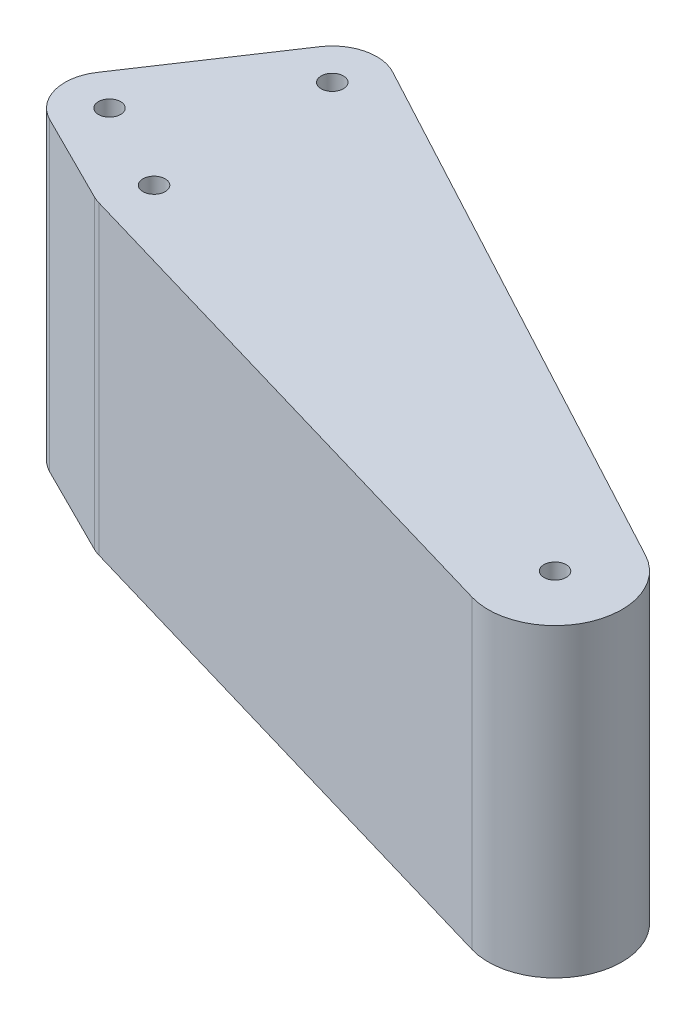
SolidWorks part; units mm, degrees
ref_plane "Front Plane" through (0, 0, 0) normal (0, 0, 1) x (1, 0, 0)
ref_plane "Top Plane" through (0, 0, 0) normal (0, 1, 0) x (1, 0, 0)
ref_plane "Right Plane" through (0, 0, 0) normal (1, 0, 0) x (0, 0, -1)
sketch "Sketch1" plane through (0, 0, 0) normal (0, 1, 0) x (1, 0, 0)
  line L1 (4.7246, 48.8135) -> (127.0868, -16.7797)
  line L2 (115.7767, -44.3932) -> (-2.8155, -9.5955)
  line L4 (-8.3205, 45.547) -> (-28.3205, 15.547)
  line L5 (-24.4721, 1.0557) -> (-4.4721, -8.9443)
  arc A0 (-8.3205, 45.547) -> (4.7246, 48.8135) centre (0, 40) cw
  arc A1 (127.0868, -16.7797) -> (115.7767, -44.3932) centre (120, -30) cw
  arc A2 (-2.8155, -9.5955) -> (-4.4721, -8.9443) centre (0, 0) cw
  arc A3 (-28.3205, 15.547) -> (-24.4721, 1.0557) centre (-20, 10) ccw
  dimension "D1" = 10
  dimension "D2" = 10
  dimension "D3" = 15
  dimension "D9" = 10
  dimension "D4" = 30
  dimension "D5" = 40
  dimension "D6" = 120
  dimension "D7" = 20
  dimension "D8" = 30
extrude "Boss-Extrude1" add sketch "Sketch1" along normal blind 17
sketch "Sketch2" plane through (0, 17, 0) normal (0, 1, 0) x (1, 0, 0)
  circle A0 centre (0, 40) radius 2.5
  circle A1 centre (0, 0) radius 2.5
  circle A2 centre (120, -30) radius 2.5
  circle A3 centre (-20, 10) radius 2.5
  arc A4 (-28.3205, 15.547) -> (-24.4721, 1.0557) centre (-20, 10) ccw construction
  dimension "D1" = 5
  dimension "D2" = 5
extrude "Cut-Extrude1" cut sketch "Sketch2" against normal through all
sketch "Sketch3" plane through (0, 17, 0) normal (0, 1, 0) x (1, 0, 0)
  line L4 (-2.8155, -9.5955) -> (115.7767, -44.3932)
  line L5 (127.0868, -16.7797) -> (4.7246, 48.8135)
  line L6 (-8.3205, 45.547) -> (-28.3205, 15.547)
  line L7 (-24.4721, 1.0557) -> (-4.4721, -8.9443)
  line L8 (-2.8155, -9.5955) -> (115.7767, -44.3932)
  line L9 (127.0868, -16.7797) -> (4.7246, 48.8135)
  line L10 (-8.3205, 45.547) -> (-28.3205, 15.547)
  line L11 (-24.4721, 1.0557) -> (-4.4721, -8.9443)
  arc A4 (-4.4721, -8.9443) -> (-2.8155, -9.5955) centre (0, 0) ccw
  arc A5 (115.7767, -44.3932) -> (127.0868, -16.7797) centre (120, -30) ccw
  arc A6 (4.7246, 48.8135) -> (-8.3205, 45.547) centre (0, 40) ccw
  arc A7 (-28.3205, 15.547) -> (-24.4721, 1.0557) centre (-20, 10) ccw
  arc A8 (-4.4721, -8.9443) -> (-2.8155, -9.5955) centre (0, 0) ccw
  arc A9 (115.7767, -44.3932) -> (127.0868, -16.7797) centre (120, -30) ccw
  arc A10 (4.7246, 48.8135) -> (-8.3205, 45.547) centre (0, 40) ccw
  arc A11 (-28.3205, 15.547) -> (-24.4721, 1.0557) centre (-20, 10) ccw
  dimension "D1" = 0
extrude "Boss-Extrude2" add sketch "Sketch3" along normal blind 51.5
sketch "Sketch4" plane through (0, 0, 0) normal (0, -1, 0) x (1, 0, 0)
  circle A0 centre (120, 30) radius 2.5 construction
  circle A1 centre (0, -40) radius 2.5 construction
  circle A2 centre (-20, -10) radius 2.5 construction
  circle A3 centre (0, 0) radius 2.5 construction
  circle A4 centre (120, 30) radius 2.5
  circle A5 centre (0, -40) radius 2.5
  circle A6 centre (-20, -10) radius 2.5
  circle A7 centre (0, 0) radius 2.5
extrude "Cut-Extrude2" cut sketch "Sketch4" against normal through all
sketch "Sketch5" plane through (21.3806, 0, -39.8849) normal (0.4725, 0, -0.8814) x (-0.8814, 0, -0.4725)
  line L0 (32.3057, 60) -> (-6.6943, 60)
  line L1 (32.3057, 68.5) -> (32.3057, 0) construction
  line L2 (-6.6943, 60) -> (-96.6943, 0)
  line L3 (-119.9362, 0) -> (18.8983, 0) construction
  line L4 (-96.6943, 0) -> (33.3057, 0)
  line L5 (33.3057, 0) -> (33.3057, 60)
  line L6 (33.3057, 60) -> (32.3057, 60)
  dimension "D1" = 60
  dimension "D2" = 90
  dimension "D3" = 1
  dimension "D4" = 130
extrude "Cut-Extrude3" [suppressed] cut sketch "Sketch5" against normal through all
sketch "Sketch6" plane through (21.3806, 0, -39.8849) normal (0.4725, 0, -0.8814) x (-0.8814, 0, -0.4725)
  line L0 (-134.9362, 8.5) -> (-99.9362, 8.5)
  line L1 (-134.9362, 68.5) -> (-134.9362, 0) construction
  line L2 (-99.9362, 8.5) -> (-14.9362, 68.5)
  line L3 (-119.9362, 68.5) -> (18.8983, 68.5) construction
  line L4 (-14.9362, 68.5) -> (-135.9362, 68.5)
  line L5 (-135.9362, 68.5) -> (-135.9362, 8.5)
  line L6 (-135.9362, 8.5) -> (-134.9362, 8.5)
  dimension "D1" = 121
  dimension "D2" = 1
  dimension "D3" = 35
  dimension "D4" = 60
extrude "Cut-Extrude4" [suppressed] cut sketch "Sketch6" against normal through all
sketch "Sketch7" [suppressed] plane through (21.3806, 0, -39.8849) normal (0.4725, 0, -0.8814) x (-0.8814, 0, -0.4725)
  line L0 (32.3057, 17) -> (-7.6943, 17)
  line L1 (32.3057, 77) -> (32.3057, 0) construction
  line L2 (-7.6943, 17) -> (-96.6943, 77)
  line L3 (-119.9362, 77) -> (18.8983, 77) construction
  line L4 (-96.6943, 77) -> (33.3057, 77)
  line L5 (33.3057, 77) -> (33.3057, 17)
  line L6 (33.3057, 17) -> (32.3057, 17)
  dimension "D1" = 1
  dimension "D2" = 130
  dimension "D3" = 60
  dimension "D4" = 40
extrude "Cut-Extrude5" [suppressed] cut sketch "Sketch7" against normal through all
sketch "Sketch8" [suppressed] plane through (21.3806, 0, -39.8849) normal (0.4725, 0, -0.8814) x (-0.8814, 0, -0.4725)
  line L0 (-14.9362, 0) -> (-99.9362, 60)
  line L1 (-119.9362, 0) -> (18.8983, 0) construction
  line L2 (-99.9362, 60) -> (-134.9362, 60)
  line L3 (-134.9362, 77) -> (-134.9362, 0) construction
  line L4 (-134.9362, 60) -> (-135.9362, 60)
  line L5 (-135.9362, 60) -> (-135.9362, 0)
  line L6 (-135.9362, 0) -> (-14.9362, 0)
  dimension "D1" = 121
  dimension "D2" = 1
  dimension "D3" = 35
  dimension "D4" = 60
extrude "Cut-Extrude6" [suppressed] cut sketch "Sketch8" against normal through all
